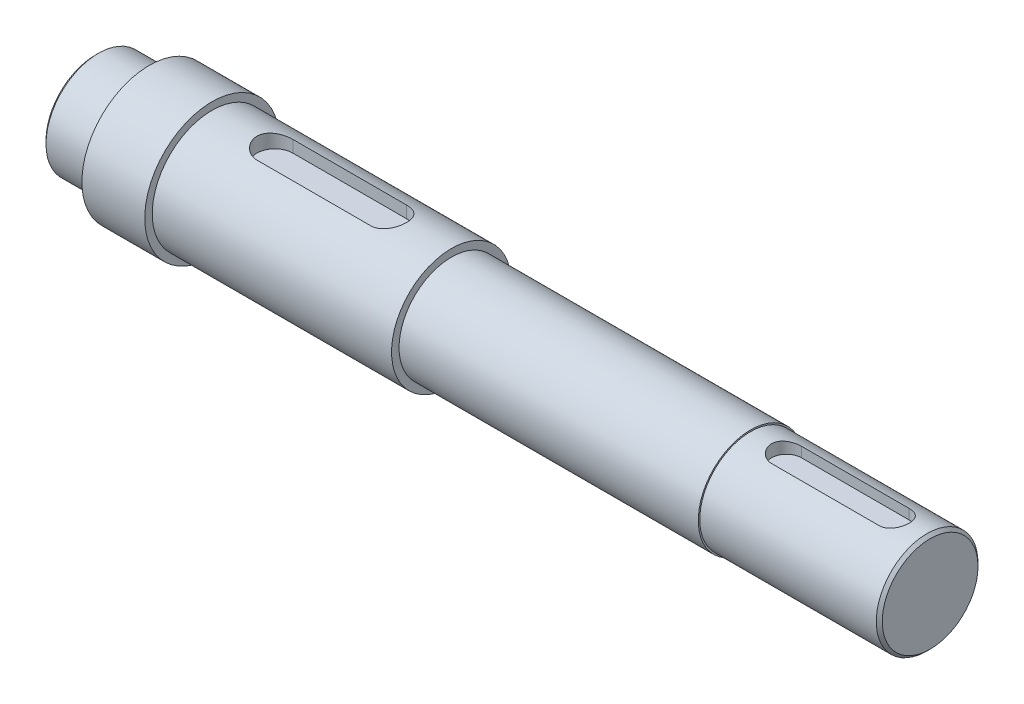
SolidWorks part; units mm, degrees
ref_plane "Front Plane" through (0, 0, 0) normal (0, 0, 1) x (1, 0, 0)
ref_plane "Top Plane" through (0, 0, 0) normal (0, 1, 0) x (1, 0, 0)
ref_plane "Right Plane" through (0, 0, 0) normal (1, 0, 0) x (0, 0, -1)
sketch "Sketch1" plane through (0, 0, 0) normal (1, 0, 0) x (0, 0, -1)
  circle A0 centre (0, 0) radius 20
  dimension "D1" = 40
extrude "Boss-Extrude1" add sketch "Sketch1" along normal blind 40 and the other way blind 40
ref_plane "Plane1" through (0, 20, 0) normal (0, 1, 0) x (1, 0, 0)
sketch "Sketch2" plane through (0, 20, 0) normal (0, 1, 0) x (1, 0, 0)
  line L0 (-19, 0) -> (19, 0) construction
  line L1 (-19, 6) -> (19, 6)
  line L2 (-19, -6) -> (19, -6)
  arc A0 (-19, 6) -> (-19, -6) centre (-19, 0) ccw
  arc A1 (19, -6) -> (19, 6) centre (19, 0) ccw
  point P2 (0, 0)
  dimension "D1" = 12
  dimension "D2" = 38
extrude "Cut-Extrude1" cut sketch "Sketch2" against normal blind 4.9
sketch "Sketch3" plane through (-40, 0, 0) normal (-1, 0, 0) x (0, 0, 1)
  circle A0 centre (0, 0) radius 22.5
  dimension "D1" = 45
extrude "Boss-Extrude2" add sketch "Sketch3" along normal blind 21
sketch "Sketch4" plane through (-61, 0, 0) normal (-1, 0, 0) x (0, 0, 1)
  circle A0 centre (0, 0) radius 17.5
  dimension "D1" = 35
extrude "Boss-Extrude3" add sketch "Sketch4" along normal blind 18
chamfer "Chamfer1" distance 1 angle 45 1 edges at (-79, 0, 17.5)
sketch "Sketch5" plane through (40, 0, 0) normal (1, 0, 0) x (0, 0, -1)
  circle A0 centre (0, 0) radius 17.5
  dimension "D1" = 35
extrude "Boss-Extrude4" add sketch "Sketch5" along normal blind 100
sketch "Sketch6" plane through (140, 0, 0) normal (1, 0, 0) x (0, 0, -1)
  circle A0 centre (0, 0) radius 17
  dimension "D1" = 34
extrude "Boss-Extrude5" add sketch "Sketch6" along normal blind 60
ref_plane "Plane2" through (0, 17, 0) normal (0, 1, 0) x (1, 0, 0)
sketch "Sketch7" plane through (0, 17, 0) normal (0, 1, 0) x (1, 0, 0)
  line L0 (170, 44.9376) -> (170, -40.9493) construction
  line L1 (140, -17.5) -> (140, 17.5) construction
  line L2 (200, -17) -> (200, 17) construction
  line L3 (152, 0) -> (188, 0) construction
  line L4 (152, 5) -> (188, 5)
  line L5 (152, -5) -> (188, -5)
  arc A0 (152, 5) -> (152, -5) centre (152, 0) ccw
  arc A1 (188, -5) -> (188, 5) centre (188, 0) ccw
  point P8 (170, 0)
  dimension "D1" = 10
  dimension "D2" = 36
extrude "Cut-Extrude2" cut sketch "Sketch7" against normal blind 4.1
chamfer "Chamfer2" distance 1 angle 45 1 edges at (200, 0, -17)
